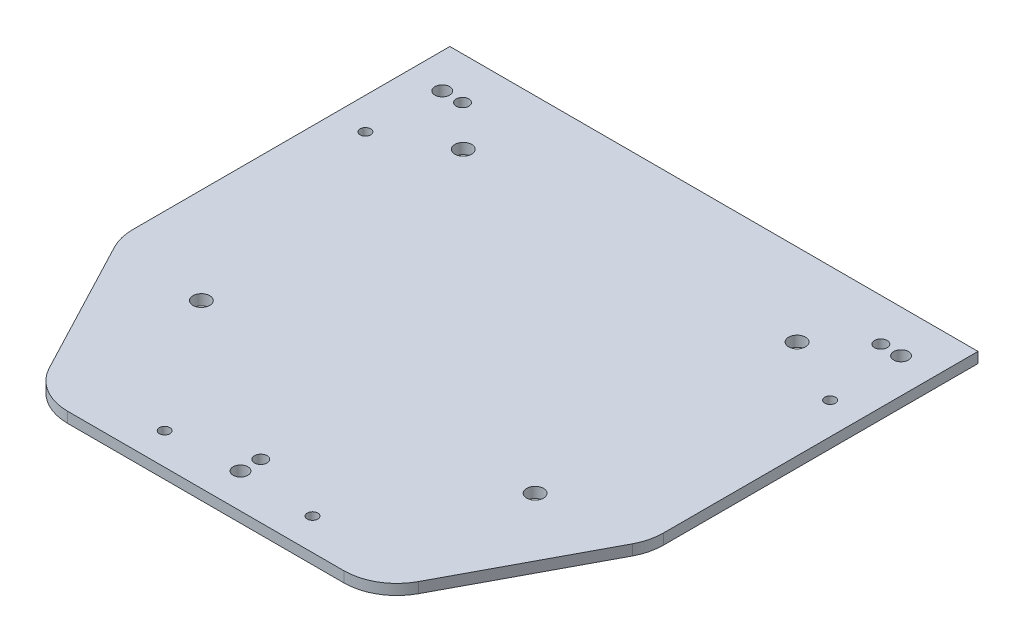
SolidWorks part; units mm, degrees
ref_plane "Plano frontal" through (0, 0, 0) normal (0, 0, 1) x (1, 0, 0)
ref_plane "Plano superior" through (0, 0, 0) normal (0, 1, 0) x (1, 0, 0)
ref_plane "Plano direito" through (0, 0, 0) normal (1, 0, 0) x (0, 0, -1)
sketch "Esboço1" plane through (0, 0, 0) normal (0, 1, 0) x (1, 0, 0)
  line L2 (399.2674, 124.203) -> (649.2674, 124.203)
  line L5 (649.2674, 124.203) -> (649.2674, 84.203)
  line L11 (646.3388, -36.4966) -> (611.2078, -102.538)
  line L12 (402.1324, -37.4447) -> (436.2433, -102.4178)
  line L14 (399.2674, 124.203) -> (399.2674, 84.203)
  line L16 (649.2674, 84.203) -> (649.2674, -24.7556)
  line L17 (399.2674, 84.203) -> (399.2674, -25.8239)
  line L18 (544.2674, -115.797) -> (589.1363, -115.797)
  line L19 (504.2674, -115.797) -> (458.3782, -115.797)
  line L23 (544.2674, -115.797) -> (504.2674, -115.797)
  arc A0 (399.2674, -25.8239) -> (402.1324, -37.4447) centre (424.2674, -25.8239) ccw
  arc A1 (436.2433, -102.4178) -> (458.3782, -115.797) centre (458.3782, -90.797) ccw
  arc A2 (589.1363, -115.797) -> (611.2078, -102.538) centre (589.1363, -90.797) ccw
  arc A3 (646.3388, -36.4966) -> (649.2674, -24.7556) centre (624.2674, -24.7556) ccw
  dimension "D4" = 40
  dimension "D5" = 40
  dimension "D6" = 25
  dimension "D16" = 40
  dimension "D2" = 250
extrude "Ressalto-extrusão4" add sketch "Esboço1" along normal blind 5 contours L14 region at (524.1456, 0, -10.511)
sketch "Esboço2" plane through (0, 5, 0) normal (0, 1, 0) x (1, 0, 0)
  line L0 (399.2674, 124.203) -> (649.2674, 124.203) construction
  line L1 (589.1363, -115.797) -> (458.3782, -115.797) construction
  line L3 (414.2674, 69.203) -> (399.2674, 69.203) construction
  line L6 (559.2674, -115.797) -> (559.2674, -100.797) construction
  line L11 (489.2674, -100.797) -> (489.2674, -115.797) construction
  line L13 (649.2674, 69.203) -> (634.2674, 69.203) construction
  circle A0 centre (559.2674, -100.797) radius 2.5
  circle A1 centre (489.2674, -100.797) radius 2.5
  circle A2 centre (634.2674, 69.203) radius 2.5
  circle A3 centre (414.2674, 69.203) radius 2.5
  dimension "D1" = 15
  dimension "D6" = 70
  dimension "D2" = 55
  dimension "D3" = 55
  dimension "D4" = 15
  dimension "D5" = 15
  dimension "D8" = 15
extrude "Corte-extrusão1" cut sketch "Esboço2" against normal blind 5
sketch "Esboço3" plane through (0, 5, 0) normal (0, 1, 0) x (1, 0, 0)
  circle A7 centre (602.5953, 85.2233) radius 4
  circle A8 centre (444.5953, 85.2233) radius 4
  circle A9 centre (602.5953, -38.7767) radius 4
  circle A10 centre (444.5953, -38.7767) radius 4
  dimension "D1" = 158
  dimension "D2" = 158
  dimension "D3" = 124
  dimension "D4" = 124
extrude "Corte-extrusão2" cut sketch "Esboço3" against normal blind 5
sketch "Esboço4" plane through (0, 5, 0) normal (0, 1, 0) x (1, 0, 0)
  line L0 (523.7573, -115.797) -> (523.7573, -99.397) construction
  line L2 (589.1363, -115.797) -> (458.3782, -115.797) construction
  line L3 (649.2674, 124.203) -> (649.2674, 104.203) construction
  line L4 (649.2674, 124.203) -> (649.2674, -24.7556) construction
  line L5 (649.2674, 104.203) -> (399.2674, 104.203) construction
  line L6 (399.2674, 124.203) -> (399.2674, -25.8239) construction
  line L7 (649.2674, 104.203) -> (632.8674, 104.203) construction
  line L8 (399.2674, 104.203) -> (415.6674, 104.203) construction
  line L9 (649.2674, 104.203) -> (623.2674, 104.203) construction
  line L10 (399.2674, 104.203) -> (425.2674, 104.203) construction
  line L11 (523.7573, -115.797) -> (523.7573, -89.797) construction
  circle A1 centre (523.7573, -99.397) radius 3.5
  circle A2 centre (632.8674, 104.203) radius 3.5
  circle A3 centre (415.6674, 104.203) radius 3.5
  circle A4 centre (623.2674, 104.203) radius 3
  circle A5 centre (425.2674, 104.203) radius 3
  circle A6 centre (523.7573, -89.797) radius 3
  dimension "D1" = 7
extrude "Corte-extrusão3" cut sketch "Esboço4" against normal blind 10
